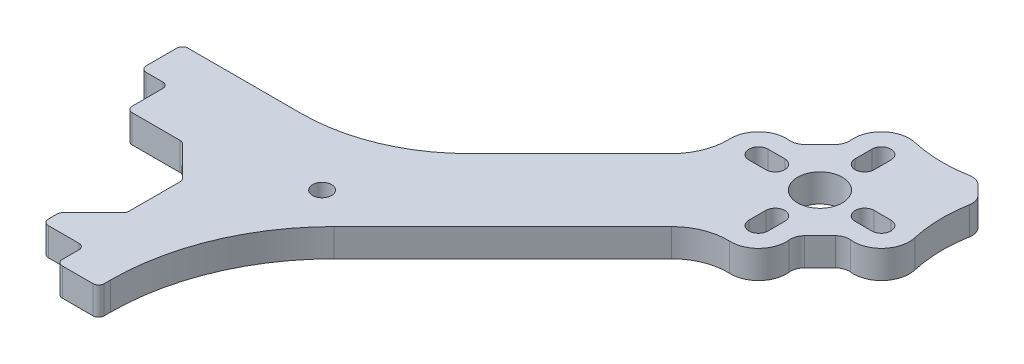
SolidWorks part; units mm, degrees
material "Thornel Mat VMA"
ref_plane "Front Plane" through (0, 0, 0) normal (0, 0, 1) x (1, 0, 0)
ref_plane "Top Plane" through (0, 0, 0) normal (0, 1, 0) x (1, 0, 0)
ref_plane "Right Plane" through (0, 0, 0) normal (1, 0, 0) x (0, 0, -1)
sketch "Sketch1" plane through (0, 0, 0) normal (0, 1, 0) x (1, 0, 0)
  line L0 (0, 37.5) -> (0, 45)
  line L4 (30, -2.1177) -> (30, 2.1177) construction
  line L5 (0, 45) -> (21.2599, 45)
  line L7 (30, 0) -> (22.5, 0)
  line L8 (22.5, 0) -> (22.5, 5)
  line L9 (22.5, 5) -> (15, 5)
  line L10 (15, 5) -> (15, 30)
  line L11 (5, 30) -> (15, 30)
  line L12 (5, 37.5) -> (5, 30)
  line L13 (0, 37.5) -> (5, 37.5)
  line L15 (0, 0) -> (79.5495, 79.5495) construction
  line L16 (30, 0) -> (30, 2.1177)
  line L17 (42.4731, 53.7868) -> (60.6301, 71.9438)
  line L18 (71.9438, 60.6301) -> (41.7157, 30.402)
  line L19 (79.5495, 87.5495) -> (79.5495, 71.5495) construction
  line L20 (79.5495, 87.5495) -> (79.5495, 90.5495) construction
  line L21 (77.8495, 87.5495) -> (77.8495, 90.5495)
  line L22 (81.2495, 87.5495) -> (81.2495, 90.5495)
  line L23 (87.5495, 79.5495) -> (90.5495, 79.5495) construction
  line L24 (87.5495, 81.2495) -> (90.5495, 81.2495)
  line L25 (87.5495, 77.8495) -> (90.5495, 77.8495)
  line L26 (79.5495, 71.5495) -> (79.5495, 68.5495) construction
  line L27 (81.2495, 71.5495) -> (81.2495, 68.5495)
  line L28 (77.8495, 71.5495) -> (77.8495, 68.5495)
  line L29 (71.5495, 79.5495) -> (68.5495, 79.5495) construction
  line L30 (71.5495, 77.8495) -> (68.5495, 77.8495)
  line L31 (71.5495, 81.2495) -> (68.5495, 81.2495)
  line L32 (71.0988, 85.2409) -> (73.8581, 88.0002)
  line L33 (85.2409, 71.0988) -> (88.0002, 73.8581)
  line L34 (91.9239, 95.4594) -> (95.4594, 91.9239)
  line L35 (93.6916, 93.6916) -> (79.5495, 79.5495) construction
  arc A0 (30, 2.1177) -> (41.7157, 30.402) centre (70, 2.1177) cw
  circle A1 centre (79.5495, 79.5495) radius 4
  arc A2 (77.8495, 87.5495) -> (81.2495, 87.5495) centre (79.5495, 87.5495) ccw
  arc A3 (81.2495, 90.5495) -> (77.8495, 90.5495) centre (79.5495, 90.5495) ccw
  arc A4 (87.5495, 81.2495) -> (87.5495, 77.8495) centre (87.5495, 79.5495) ccw
  arc A5 (90.5495, 77.8495) -> (90.5495, 81.2495) centre (90.5495, 79.5495) ccw
  arc A6 (81.2495, 71.5495) -> (77.8495, 71.5495) centre (79.5495, 71.5495) ccw
  arc A7 (77.8495, 68.5495) -> (81.2495, 68.5495) centre (79.5495, 68.5495) ccw
  arc A8 (71.5495, 77.8495) -> (71.5495, 81.2495) centre (71.5495, 79.5495) ccw
  arc A9 (68.5495, 81.2495) -> (68.5495, 77.8495) centre (68.5495, 79.5495) ccw
  arc A10 (63.5527, 79.3713) -> (69.0705, 84.5223) centre (68.5495, 79.5495) cw
  arc A11 (74.5767, 90.0285) -> (80.6607, 95.4245) centre (79.5495, 90.5495) cw
  arc A12 (80.6607, 95.4245) -> (91.9239, 95.4594) centre (86.2167, 119.7993) ccw
  arc A13 (69.0705, 84.5223) -> (71.0988, 85.2409) centre (69.331, 87.0087) ccw
  arc A14 (63.5527, 79.3713) -> (60.6301, 71.9438) centre (53.559, 79.0149) cw
  arc A15 (73.8581, 88.0002) -> (74.5767, 90.0285) centre (72.0903, 89.768) ccw
  arc A16 (95.4245, 80.6607) -> (95.4594, 91.9239) centre (119.7993, 86.2167) cw
  arc A17 (90.0285, 74.5767) -> (95.4245, 80.6607) centre (90.5495, 79.5495) ccw
  arc A18 (88.0002, 73.8581) -> (90.0285, 74.5767) centre (89.768, 72.0903) cw
  arc A19 (84.5223, 69.0705) -> (85.2409, 71.0988) centre (87.0087, 69.331) cw
  arc A20 (79.3713, 63.5527) -> (84.5223, 69.0705) centre (79.5495, 68.5495) ccw
  arc A21 (79.3713, 63.5527) -> (71.9438, 60.6301) centre (79.0149, 53.559) ccw
  arc A22 (21.2599, 45) -> (42.4731, 53.7868) centre (21.2599, 75) ccw
  point P0 (0, 0)
  point P14 (10.6299, 45)
  point P21 (79.5495, 89.0495)
  point P29 (79.5495, 79.5495)
  point P33 (89.0495, 79.5495)
  point P40 (79.5495, 70.0495)
  point P47 (70.0495, 79.5495)
  point P54 (79.5495, 79.5495)
  dimension "D11" = 8
  dimension "D13" = 1.7
  dimension "D17" = 5
  dimension "D18" = 25
  dimension "D22" = 2.5
  dimension "D23" = 10
  dimension "D24" = 30
  dimension "D26" = 40
  dimension "D3" = 30
  dimension "D4" = 8
  dimension "D5" = 7.5
  dimension "D6" = 15
  dimension "D7" = 5
  dimension "D8" = 45
  dimension "D9" = 112.5
  dimension "D10" = 45
  dimension "D12" = 45
  dimension "D14" = 3
  dimension "D15" = 8
  dimension "D19" = 20
  dimension "D20" = 2.5
  dimension "D21" = 10
  dimension "D25" = 15
  dimension "D16" = 4
extrude "Boss-Extrude1" add sketch "Sketch1" along normal mid plane 5 contours A21 A20 A19 L33 A18 A17 A16 L34 A12 A11 A15 L32 A13 A10 A14 L17 L13 L12 L11 L10 L9 L8 L7 L16 A0 L18 A9 L31 A8 L30 A7 L28 A6 L27 A5 L25 A4 L24 A3 L22 A2 L21 A1 region at (46.1308, 0, -48.4988)
sketch "Sketch2" plane through (0, 2.5, 0) normal (0, 1, 0) x (1, 0, 0)
  line L0 (15, 30) -> (21, 24)
  line L1 (21, 24) -> (21, 14)
  line L2 (21, 14) -> (15, 8)
  line L15 (21.2599, 45) -> (0, 45)
  line L16 (0, 45) -> (0, 37.5)
  line L17 (0, 37.5) -> (5, 37.5)
  line L18 (5, 37.5) -> (5, 30)
  line L19 (5, 30) -> (15, 30)
  line L20 (15, 30) -> (15, 5)
  line L21 (15, 5) -> (22.5, 5)
  line L22 (22.5, 5) -> (22.5, 0)
  line L23 (22.5, 0) -> (30, 0)
  line L24 (30, 0) -> (30, 2.1177)
  line L25 (41.7157, 30.402) -> (71.9438, 60.6301)
  line L26 (85.2409, 71.0988) -> (88.0002, 73.8581)
  line L27 (95.4594, 91.9239) -> (91.9239, 95.4594)
  line L28 (73.8581, 88.0002) -> (71.0988, 85.2409)
  line L29 (60.6301, 71.9438) -> (42.4731, 53.7868)
  line L30 (21.2599, 45) -> (0, 45)
  line L31 (0, 45) -> (0, 37.5)
  line L32 (0, 37.5) -> (5, 37.5)
  line L33 (5, 37.5) -> (5, 30)
  line L34 (5, 30) -> (15, 30)
  line L35 (15, 30) -> (15, 5)
  line L36 (15, 5) -> (22.5, 5)
  line L37 (22.5, 5) -> (22.5, 0)
  line L38 (22.5, 0) -> (30, 0)
  line L39 (30, 0) -> (30, 2.1177)
  line L40 (41.7157, 30.402) -> (71.9438, 60.6301)
  line L41 (85.2409, 71.0988) -> (88.0002, 73.8581)
  line L42 (95.4594, 91.9239) -> (91.9239, 95.4594)
  line L43 (73.8581, 88.0002) -> (71.0988, 85.2409)
  line L44 (60.6301, 71.9438) -> (42.4731, 53.7868)
  arc A14 (21.2599, 45) -> (42.4731, 53.7868) centre (21.2599, 75) ccw
  arc A15 (41.7157, 30.402) -> (30, 2.1177) centre (70, 2.1177) ccw
  arc A16 (79.3713, 63.5527) -> (71.9438, 60.6301) centre (79.0149, 53.559) ccw
  arc A17 (79.3713, 63.5527) -> (84.5223, 69.0705) centre (79.5495, 68.5495) ccw
  arc A18 (85.2409, 71.0988) -> (84.5223, 69.0705) centre (87.0087, 69.331) ccw
  arc A19 (90.0285, 74.5767) -> (88.0002, 73.8581) centre (89.768, 72.0903) ccw
  arc A20 (90.0285, 74.5767) -> (95.4245, 80.6607) centre (90.5495, 79.5495) ccw
  arc A21 (95.4594, 91.9239) -> (95.4245, 80.6607) centre (119.7993, 86.2167) ccw
  arc A22 (80.6607, 95.4245) -> (91.9239, 95.4594) centre (86.2167, 119.7993) ccw
  arc A23 (80.6607, 95.4245) -> (74.5767, 90.0285) centre (79.5495, 90.5495) ccw
  arc A24 (73.8581, 88.0002) -> (74.5767, 90.0285) centre (72.0903, 89.768) ccw
  arc A25 (69.0705, 84.5223) -> (71.0988, 85.2409) centre (69.331, 87.0087) ccw
  arc A26 (69.0705, 84.5223) -> (63.5527, 79.3713) centre (68.5495, 79.5495) ccw
  arc A27 (60.6301, 71.9438) -> (63.5527, 79.3713) centre (53.559, 79.0149) ccw
  arc A28 (21.2599, 45) -> (42.4731, 53.7868) centre (21.2599, 75) ccw
  arc A29 (41.7157, 30.402) -> (30, 2.1177) centre (70, 2.1177) ccw
  arc A30 (79.3713, 63.5527) -> (71.9438, 60.6301) centre (79.0149, 53.559) ccw
  arc A31 (79.3713, 63.5527) -> (84.5223, 69.0705) centre (79.5495, 68.5495) ccw
  arc A32 (85.2409, 71.0988) -> (84.5223, 69.0705) centre (87.0087, 69.331) ccw
  arc A33 (90.0285, 74.5767) -> (88.0002, 73.8581) centre (89.768, 72.0903) ccw
  arc A34 (90.0285, 74.5767) -> (95.4245, 80.6607) centre (90.5495, 79.5495) ccw
  arc A35 (95.4594, 91.9239) -> (95.4245, 80.6607) centre (119.7993, 86.2167) ccw
  arc A36 (80.6607, 95.4245) -> (91.9239, 95.4594) centre (86.2167, 119.7993) ccw
  arc A37 (80.6607, 95.4245) -> (74.5767, 90.0285) centre (79.5495, 90.5495) ccw
  arc A38 (73.8581, 88.0002) -> (74.5767, 90.0285) centre (72.0903, 89.768) ccw
  arc A39 (69.0705, 84.5223) -> (71.0988, 85.2409) centre (69.331, 87.0087) ccw
  arc A40 (69.0705, 84.5223) -> (63.5527, 79.3713) centre (68.5495, 79.5495) ccw
  arc A41 (60.6301, 71.9438) -> (63.5527, 79.3713) centre (53.559, 79.0149) ccw
  line M39 (15, 30) -> (15, 5)
  dimension "D2" = 135
  dimension "D3" = 6
  dimension "D4" = 3
  dimension "D1" = 0
extrude "Cut-Extrude1" cut sketch "Sketch2" against normal blind 10 contours L2 L1 L0 M39 region at (17.625, 2.5, -19)
fillet "Fillet1" radius 2.5 2 edges at (95.4594, 0, -91.9239) (91.9239, 0, -95.4594)
fillet "Fillet2" radius 1 12 edges at (22.5, 0, 0) (22.5, 0, -5) (15, 0, -5) (5, 0, -30) (5, 0, -37.5) (30, 0, 0) (0, 0, -45) (0, 0, -37.5) (15, 0, -8) (21, 0, -14) (21, 0, -24) (15, 0, -30)
hole_wizard "M3 Clearance Hole1" positions "Sketch3" profile "Sketch4" hole size "M3" standard "ANSI Metric" end condition through all
sketch "Sketch3" plane through (0, 2.5, 0) normal (0, 1, 0) x (1, 0, 0)
  point P1 (35, 35)
  dimension "D1" = 35
  dimension "D2" = 35
sketch "Sketch4" plane through (35, 2.5, -35) normal (1, 0, 0) x (0, 0, 1)
  line L0 (0, 0) -> (0, 5)
  line L1 (0, 5) -> (1.7, 5)
  line L2 (1.7, 5) -> (1.7, 0)
  line L5 (1.7, 0) -> (0, 0)
  line L11 (0, -6.35) -> (0, 107.95) construction
  dimension "Thru Hole Dia." = 3.4
  dimension "Thru Hole Depth" = 5
